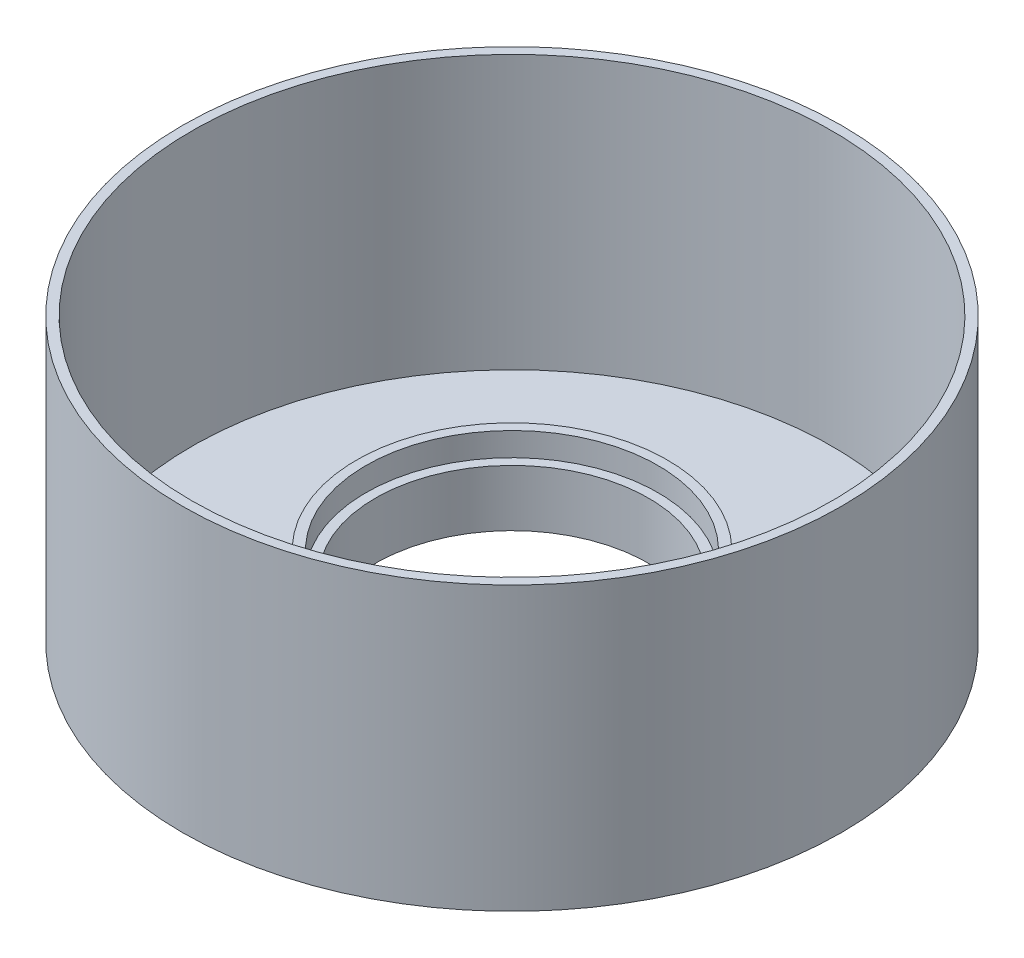
SolidWorks part; units mm, degrees
ref_plane "Front Plane" through (0, 0, 0) normal (0, 0, 1) x (1, 0, 0)
ref_plane "Top Plane" through (0, 0, 0) normal (0, 1, 0) x (1, 0, 0)
ref_plane "Right Plane" through (0, 0, 0) normal (1, 0, 0) x (0, 0, -1)
sketch "Sketch1" plane through (0, 0, 0) normal (0, 1, 0) x (1, 0, 0)
  circle A0 centre (0, 0) radius 70
  dimension "D1" = 140
extrude "Boss-Extrude1" add sketch "Sketch1" along normal blind 60
shell "Shell1" thickness 2 removed face at (0, 60, 70)
sketch "Sketch2" plane through (0, 2, 0) normal (0, 1, 0) x (1, 0, 0)
  circle A0 centre (0, 0) radius 29
  dimension "D1" = 58
extrude "Extrude-Thin1" add sketch "Sketch2" along normal blind 15 thin thin type one direction wall 4
sketch "Sketch3" plane through (0, 17, 0) normal (0, 1, 0) x (1, 0, 0)
  circle A0 centre (0, 0) radius 31
  dimension "D1" = 62
extrude "Cut-Extrude1" cut sketch "Sketch3" against normal blind 5
sketch "Sketch4" plane through (0, 2, 0) normal (0, 1, 0) x (1, 0, 0)
  circle A0 centre (0, 0) radius 29
extrude "Cut-Extrude2" cut sketch "Sketch4" against normal blind 2
